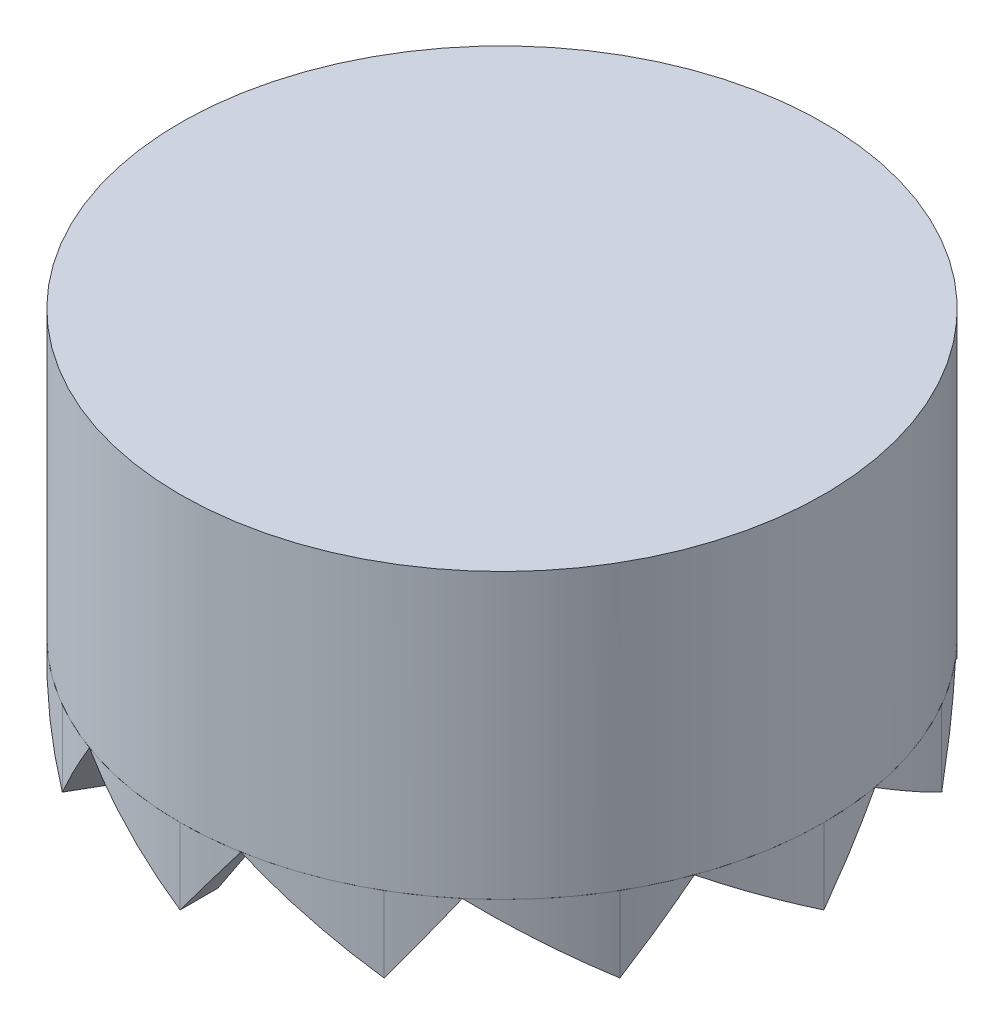
SolidWorks part; units mm, degrees
ref_plane "前视基准面" through (0, 0, 0) normal (0, 0, 1) x (1, 0, 0)
ref_plane "上视基准面" through (0, 0, 0) normal (0, 1, 0) x (1, 0, 0)
ref_plane "右视基准面" through (0, 0, 0) normal (1, 0, 0) x (0, 0, -1)
other "Configuration Table"
sketch "草图7" plane through (0, 0, 0) normal (0, -1, 0) x (1, 0, 0)
  circle A0 centre (0, 0) radius 34
  circle A1 centre (0, 0) radius 30
  dimension "D1" = 68
  dimension "D2" = 60
extrude "凸台-拉伸3" add sketch "草图7" along normal blind 20
sketch "草图9" plane through (0, -20, 0) normal (0, -1, 0) x (1, 0, 0)
  circle A0 centre (0, 0) radius 35
sketch "草图11" plane through (0, -20, 0) normal (0, -1, 0) x (1, 0, 0)
  line L0 (0, 0) -> (0, 35) construction
  line L1 (0, 0) -> (6.0777, 34.4683) construction
  line L2 (0, 0) -> (-11.9707, 32.8892) construction
  line L3 (-11.9707, 32.8892) -> (-10.2606, 28.1908)
  line L4 (6.0777, 34.4683) -> (5.2094, 29.5442)
  line L5 (0, 35) -> (0, 30)
  arc A0 (6.0777, 34.4683) -> (-11.9707, 32.8892) centre (0, 0) ccw
  arc A1 (5.2094, 29.5442) -> (-10.2606, 28.1908) centre (0, 0) ccw
  circle M4 centre (0, 0) radius 34
  dimension "D1" = 70
  dimension "D2" = 60
  dimension "D3" = 20
  dimension "D4" = 10
extrude "凸台-拉伸5" add sketch "草图11" along normal blind 8 separate body contours A1 L5 L3 M4 region at (-5.5358, -20, 31.3949)
sketch "草图12" plane through (0, -28, 0) normal (0, -1, 0) x (1, 0, 0)
  circle A0 centre (0, 0) radius 35
  dimension "D1" = 70
curve "螺旋线/涡状线3" pitch 144 height 144 radius 35 left hand yes centre (0, -28, 0) axis (0, 1, 0) start towards (0, 0, 1)
sketch "草图13" plane through (0, 0, 0) normal (1, 0, 0) x (0, 0, -1)
  line L5 (-30, -28) -> (-45.7979, -28)
  line L6 (-30, -28) -> (-30, -77.5358)
  line L7 (-30, -77.5358) -> (-45.7979, -77.5358)
  line L8 (-45.7979, -28) -> (-45.7979, -77.5358)
sweep "切除-扫描5" cut profiles "草图13" path "螺旋线/涡状线3" align with end faces yes
extrude "凸台-拉伸6" add sketch "草图11<3>" along normal blind 10 separate body contours A1 L4 L5 M4 region at (2.7891, -20, 31.8792)
sketch "草图11<3>" plane through (0, -20, 0) normal (0, -1, 0) x (1, 0, 0) same geometry as "草图11"
ref_plane "基准面1" through (0, -30, 0) normal (0, -1, 0) x (-1, 0, 0)
sketch "草图23" plane through (0, -30, 0) normal (0, -1, 0) x (-1, 0, 0)
  circle A0 centre (0, 0) radius 35
curve "螺旋线/涡状线5" pitch 288 height 288 radius 35 centre (0, -30, 0) axis (0, 1, 0) start towards (0, 0, 1)
sweep "切除-扫描7" cut profiles "草图13<3>" path "螺旋线/涡状线5" align with end faces yes
sketch "草图13<3>" plane through (0, 0, 0) normal (1, 0, 0) x (0, 0, -1) same geometry as "草图13"
pattern_circular "阵列(圆周)4" count 12 over 360 about axis through (0, -20, 0) along (0, 1, 0) of "凸台-拉伸6" reverse direction yes
pattern_circular "阵列(圆周)5" count 12 over 360 about axis through (0, -20, 0) along (0, 1, 0) of "凸台-拉伸3"
sketch "草图24" plane through (0, 0, 0) normal (0, 1, 0) x (1, 0, 0)
  circle A0 centre (0, 0) radius 34
  dimension "D1" = 68
extrude "凸台-拉伸7" add sketch "草图24" along normal blind 10
